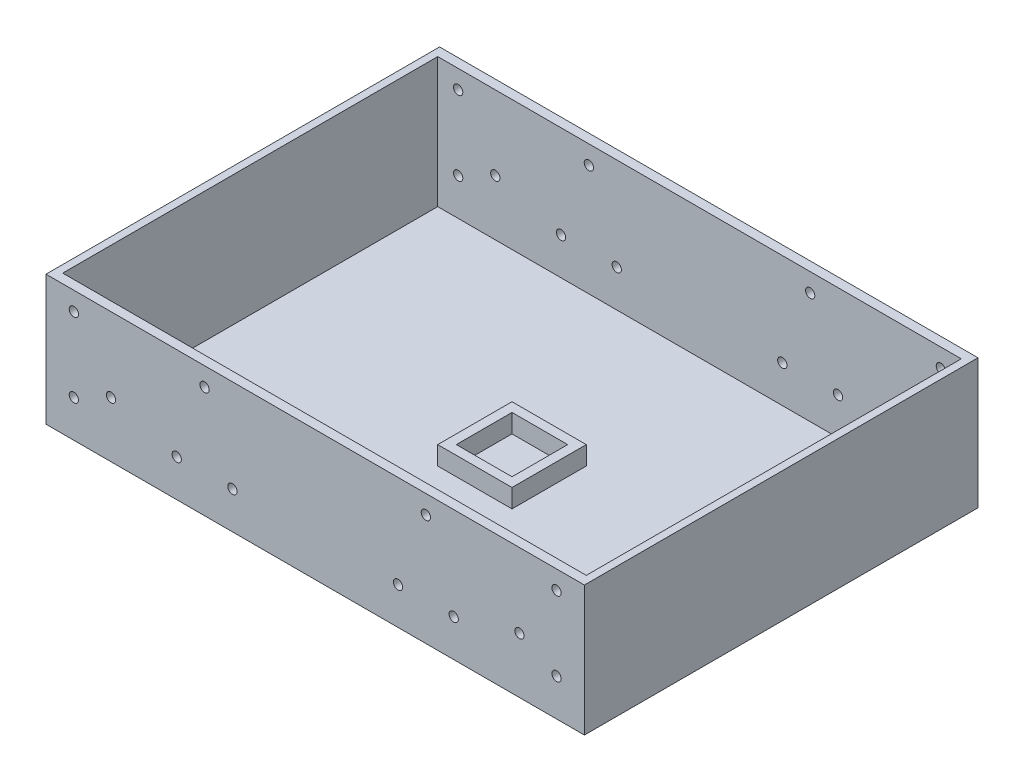
SolidWorks part; units mm, degrees
note: '?' marks a value the reader was unsure of.
ref_plane "Front Plane" through (0, 0, 0) normal (0, 0, 1) x (1, 0, 0)
ref_plane "Top Plane" through (0, 0, 0) normal (0, 1, 0) x (1, 0, 0)
ref_plane "Right Plane" through (0, 0, 0) normal (1, 0, 0) x (0, 0, -1)
sketch "Sketch1" plane through (0, 0, 0) normal (0, 1, 0) x (1, 0, 0)
  line L1 (-145, -106) -> (145, -106)
  line L2 (-145, -106) -> (-145, 106)
  line L3 (-145, 106) -> (145, 106)
  line L4 (145, -106) -> (145, 106)
  line L5 (-145, -106) -> (145, 106) construction
  line L6 (-145, 106) -> (145, -106) construction
  point P0 (0, 0)
  dimension "D1" = 290
  dimension "D2" = 212
extrude "Boss-Extrude1" add sketch "Sketch1" along normal blind 10
sketch "Sketch2" plane through (0, 10, 0) normal (0, 1, 0) x (1, 0, 0)
  line L5 (-141, -101) -> (141, -101)
  line L6 (-141, -101) -> (-141, 101)
  line L7 (-141, 101) -> (141, 101)
  line L16 (145, -106) -> (145, 106)
  line L17 (145, 106) -> (-145, 106)
  line L18 (-145, 106) -> (-145, -106)
  line L19 (-145, -106) -> (145, -106)
  line L20 (145, -106) -> (145, 106)
  line L21 (145, 106) -> (-145, 106)
  line L22 (-145, 106) -> (-145, -106)
  line L23 (-145, -106) -> (145, -106)
  line L24 (141, -101) -> (141, 101)
  line L25 (-141, -101) -> (141, 101) construction
  line L26 (-141, 101) -> (141, -101) construction
  point P2 (0, 0)
  dimension "D1" = 282
  dimension "D3" = 202
  dimension "D2" = 0
extrude "Boss-Extrude2" add sketch "Sketch2" along normal blind 70
sketch "Sketch3" plane through (0, 10, 0) normal (0, 1, 0) x (1, 0, 0)
  line L0 (-135, 115) -> (-135, -115)
  line L1 (-135, -115) -> (135, -115)
  line L2 (135, -115) -> (135, 115)
  line L3 (135, 115) -> (-135, 115)
  line L4 (-141, -101) -> (141, -101)
  line L5 (-141, -101) -> (141, -101)
  line L6 (141, -101) -> (141, 101)
  line L7 (141, -101) -> (141, 101)
  line L13 (-15, -15) -> (15, -15)
  line L14 (-15, -15) -> (-15, 15)
  line L15 (-15, 15) -> (15, 15)
  line L16 (15, -15) -> (15, 15)
  line L17 (-15, -15) -> (15, 15) construction
  line L18 (-15, 15) -> (15, -15) construction
  line L19 (-20, -20) -> (20, -20)
  line L20 (-20, -20) -> (-20, 20)
  line L21 (-20, 20) -> (20, 20)
  line L22 (20, -20) -> (20, 20)
  line L23 (-20, -20) -> (20, 20) construction
  line L24 (-20, 20) -> (20, -20) construction
  line L28 (141, 101) -> (-141, 101)
  line L29 (141, 101) -> (-141, 101)
  line L30 (-141, 101) -> (-141, -101)
  line L31 (-141, 101) -> (-141, -101)
  point P8 (0, 0)
  point P14 (0, 0)
  dimension "D3" = 30
  dimension "D4" = 5
  dimension "D1" = 0
extrude "Boss-Extrude3" add sketch "Sketch3" along normal blind 10
chamfer "Chamfer1" distance 10 angle 45 4 edges at (0, 0, -106) (-145, 0, 0) (0, 0, 106) (145, 0, 0)
sketch "Sketch4" plane through (0, 0, 106) normal (0, 0, 1) x (1, 0, 0)
  line L0 (-74.6, 30) -> (-44.6, 30) construction
  line L1 (-145, 10) -> (145, 10) construction
  circle A0 centre (-44.6, 30) radius 2.5
  circle A1 centre (-74.6, 30) radius 2.5
  circle A2 centre (-59.6, 70) radius 2.5
  point P6 (-59.6, 30)
  dimension "D1" = 5
  dimension "D2" = 30
  dimension "D3" = 40
  dimension "D4" = 20
  dimension "D5" = 59.6
extrude "Cut-Extrude1" cut sketch "Sketch4" against normal up to surface (207 mm away)
ref_axis "Axis1" [suppressed] through (0, 84, 0) along (0, -1, 0)?
pattern_circular "CirPattern1" [suppressed] count 2 over 360 about axis through (0, 84, 0) along (0, -1, 0)
sketch "Sketch5" plane through (0, 0, 106) normal (0, 0, 1) x (1, 0, 0)
  line L0 (-145, 10) -> (145, 10) construction
  line L1 (-145, 80) -> (-145, 10) construction
  circle A0 centre (-130, 70) radius 2.5
  circle A1 centre (-130, 30) radius 2.5
  circle A2 centre (-110, 40) radius 2.5
  dimension "D1" = 5
  dimension "D2" = 40
  dimension "D3" = 20
  dimension "D4" = 15
  dimension "D5" = 30
  dimension "D6" = 20
extrude "Cut-Extrude2" cut sketch "Sketch5" against normal through all
mirror "Mirror1" about plane through (0, 0, 0) normal (1, 0, 0) of "Cut-Extrude2"
mirror "Mirror2" about plane through (0, 0, 0) normal (1, 0, 0) of "Cut-Extrude1" second plane through (0, 0, 0) second plane normal (0, 0, 1)
